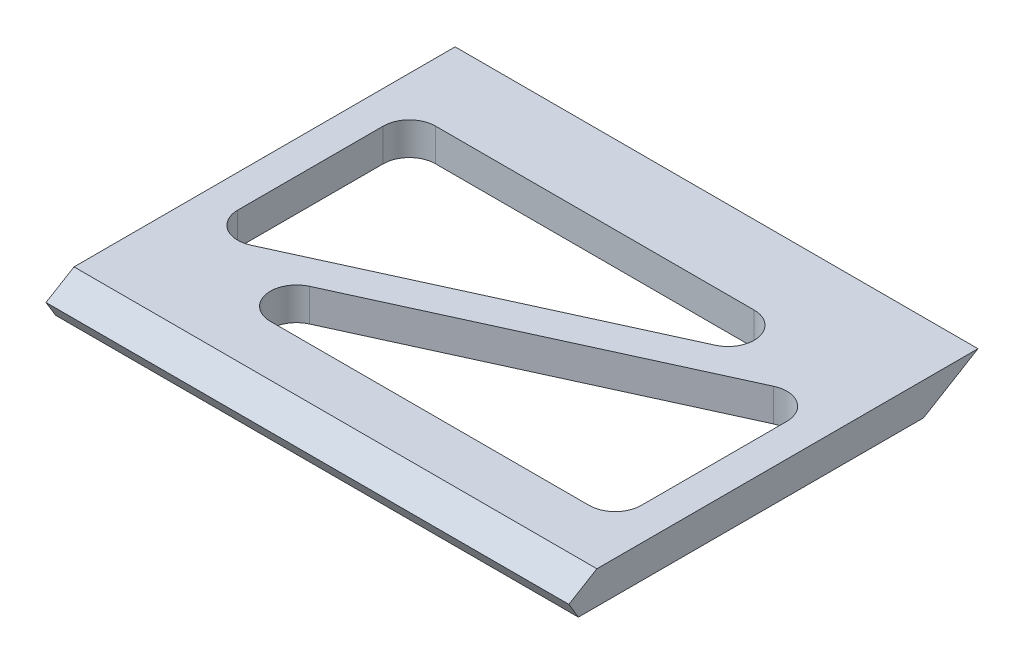
SolidWorks part; units mm, degrees
material "Balsa"
ref_plane "Front Plane" through (0, 0, 0) normal (0, 0, 1) x (1, 0, 0)
ref_plane "Top Plane" through (0, 0, 0) normal (0, 1, 0) x (1, 0, 0)
ref_plane "Right Plane" through (0, 0, 0) normal (1, 0, 0) x (0, 0, -1)
sketch "Sketch3" plane through (71.1933, 0, 0) normal (1, 0, 0) x (0, 0, -1)
  line L0 (56.968, 6.35) -> (46.3846, 0)
  line L1 (46.3846, 0) -> (-20.6804, 0)
  line L2 (-20.6804, 0) -> (-22.5302, 3.083)
  line L3 (-22.5302, 3.083) -> (-32.9848, 20.5072) construction
  line L5 (56.9676, 6.3498) -> (89.6381, 25.9521) construction
  line L6 (-22.5302, 3.083) -> (-17.0851, 6.35)
  line L7 (-17.0851, 6.35) -> (56.968, 6.35)
extrude "Boss-Extrude2" add sketch "Sketch3" against normal up to surface (101.6 mm away)
sketch "Sketch4" plane through (0, 6.35, 0) normal (0, 1, 0) x (1, 0, 0)
  line L0 (-30.4067, -17.0851) -> (-30.4067, 56.968) construction
  line L1 (-18.9767, 41.728) -> (42.949, 41.728)
  line L2 (-24.0567, 36.648) -> (-24.0567, 8.3732)
  line L3 (-2.1624, -7.1791) -> (59.7633, -7.1791)
  line L4 (64.8433, 26.1757) -> (64.8433, -2.0991)
  line L5 (-30.4067, 56.968) -> (71.1933, 56.968) construction
  line L6 (71.1933, 56.968) -> (71.1933, -17.0851) construction
  line L7 (-30.4067, -17.0851) -> (71.1933, -17.0851) construction
  line L8 (-16.8668, 3.7521) -> (45.0589, 32.0269)
  line L9 (-4.2724, 2.522) -> (57.6533, 30.7968)
  line L10 (-29.6117, -5.5575) -> (68.6464, 39.3064)
  arc A0 (-4.2724, 2.522) -> (-2.1624, -7.1791) centre (-2.1624, -2.0991) ccw
  arc A1 (59.7633, -7.1791) -> (64.8433, -2.0991) centre (59.7633, -2.0991) ccw
  arc A2 (57.6533, 30.7968) -> (64.8433, 26.1757) centre (59.7633, 26.1757) cw
  arc A3 (45.0589, 32.0269) -> (42.949, 41.728) centre (42.949, 36.648) ccw
  arc A4 (-18.9767, 41.728) -> (-24.0567, 36.648) centre (-18.9767, 36.648) ccw
  arc A5 (-16.8668, 3.7521) -> (-24.0567, 8.3732) centre (-18.9767, 8.3732) cw
  dimension "D7" = 5.08
  dimension "D1" = 6.35
  dimension "D2" = 15.24
  dimension "D3" = 6.35
  dimension "D4" = 9.906
  dimension "D5" = 3.175
  dimension "D6" = 3.175
extrude "Cut-Extrude1" cut sketch "Sketch4" against normal up to surface (6.35 mm away) contours A5 L8 A3 L1 A4 L2 | A2 L9 A0 L3 A1 L4 region at (4.1335, 6.35, -27.6167) region at (36.6531, 6.35, -6.9321) up to face at (20.3933, 0, -12.8521)
